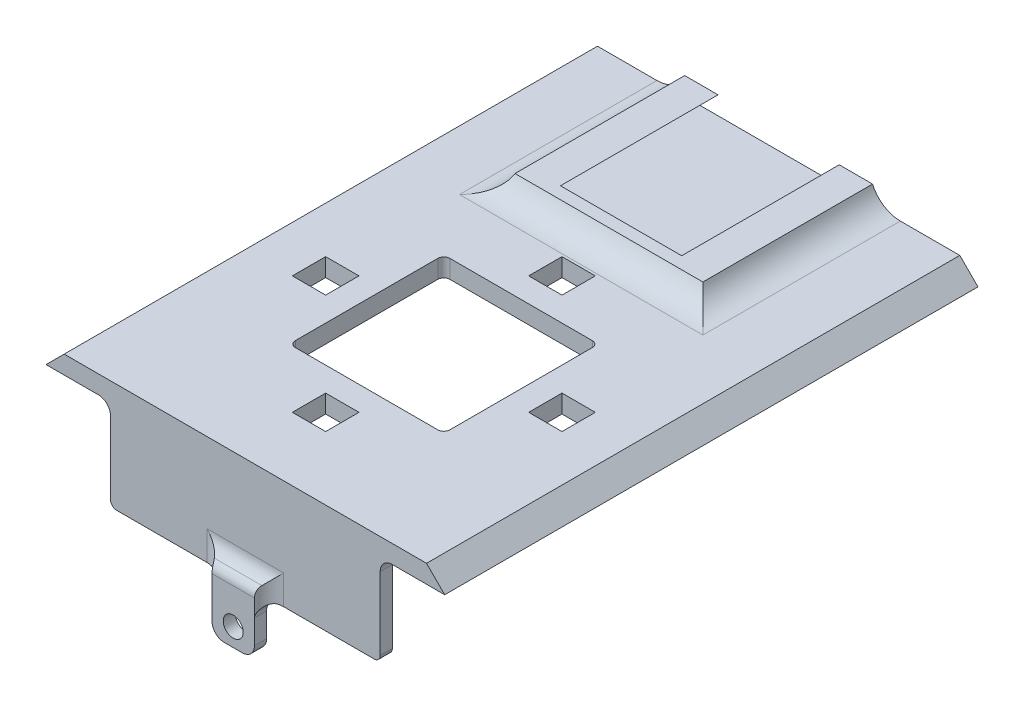
SolidWorks part; units mm, degrees
ref_plane "Front Plane" through (0, 0, 0) normal (0, 0, 1) x (1, 0, 0)
ref_plane "Top Plane" through (0, 0, 0) normal (0, 1, 0) x (1, 0, 0)
ref_plane "Right Plane" through (0, 0, 0) normal (1, 0, 0) x (0, 0, -1)
sketch "Sketch1" plane through (0, 0, 0) normal (0, 0, 1) x (1, 0, 0)
  line L0 (33.5, 0) -> (-33.5, 0) construction
  line L1 (-33.5, 0) -> (-30, 3.5) construction
  line L2 (-30, 3.5) -> (30, 3.5) construction
  line L3 (30, 3.5) -> (33.5, 0) construction
  line L4 (29.8964, 3.25) -> (32.8964, 0.25)
  line L5 (32.8964, 0.25) -> (-32.8964, 0.25)
  line L6 (-32.8964, 0.25) -> (-29.8964, 3.25)
  line L7 (-29.8964, 3.25) -> (29.8964, 3.25)
  point P4 (0, 0)
  dimension "D1" = 45
  dimension "D2" = 45
  dimension "D3" = 3
  dimension "D4" = 67
  dimension "D5" = 0.25
extrude "Boss-Extrude1" add sketch "Sketch1" against normal blind 88
sketch "Sketch2" plane through (0, 0, 0) normal (0, 0, 1) x (1, 0, 0)
  line L0 (-32.8964, 0.25) -> (32.8964, 0.25) construction
  line L1 (-22.25, 0.25) -> (22.25, 0.25)
  line L2 (-22.25, 0.25) -> (-22.25, -14.75)
  line L3 (-22.25, -14.75) -> (22.25, -14.75)
  line L4 (22.25, 0.25) -> (22.25, -14.75)
  line L5 (-22.25, 0.25) -> (22.25, -14.75) construction
  line L6 (-22.25, -14.75) -> (22.25, 0.25) construction
  point P0 (0, -7.25)
  dimension "D1" = 15
  dimension "D2" = 44.5
extrude "Boss-Extrude2" add sketch "Sketch2" against normal blind 2
sketch "Sketch3" plane through (0, 0, 0) normal (0, 0, 1) x (1, 0, 0)
  line L0 (-22.25, -14.75) -> (22.25, -14.75) construction
  line L1 (3.5, -22.75) -> (-3.5, -22.75)
  line L2 (3.5, -22.75) -> (3.5, -12.75)
  line L3 (3.5, -12.75) -> (-3.5, -12.75)
  line L4 (-3.5, -22.75) -> (-3.5, -12.75)
  line L5 (3.5, -22.75) -> (-3.5, -12.75) construction
  line L6 (3.5, -12.75) -> (-3.5, -22.75) construction
  circle A0 centre (0, -19.75) radius 1.65
  point P0 (0, -17.75)
  dimension "D4" = 3.3
  dimension "D1" = 8
  dimension "D2" = 2
  dimension "D3" = 7
  dimension "D5" = 5
extrude "Boss-Extrude3" add sketch "Sketch3" along normal blind 2
fillet "Fillet1" radius 3 3 edges at (3.5, -13.75, 0) (-3.5, -13.75, 0) (0, -12.75, 0)
fillet "Fillet2" radius 2 2 edges at (3.5, -14.75, 1) (-3.5, -14.75, 1)
fillet "Fillet3" radius 2 2 edges at (-3.5, -22.75, 1) (3.5, -22.75, 1)
fillet "Fillet4" radius 2 1 edges at (0, -12.75, 2)
fillet "Fillet5" radius 0.5 1 edges at (0, -14.75, 0)
fillet "Fillet6" radius 1 2 edges at (22.25, -14.75, -1) (-22.25, -14.75, -1)
fillet "Fillet7" radius 2 3 edges at (22.25, 0.25, -1) (0, 0.25, -2) (-22.25, 0.25, -1)
sketch "Sketch4" plane through (0, 3.25, 0) normal (0, 1, 0) x (1, 0, 0)
  line L0 (29.8964, 0) -> (-29.8964, 0) construction
  line L1 (12.75, 20) -> (-12.75, 20)
  line L2 (12.75, 20) -> (12.75, 45.5)
  line L3 (12.75, 45.5) -> (-12.75, 45.5)
  line L4 (-12.75, 20) -> (-12.75, 45.5)
  line L5 (12.75, 20) -> (-12.75, 45.5) construction
  line L6 (12.75, 45.5) -> (-12.75, 20) construction
  line L7 (-19.5, 32.75) -> (19.5, 32.75) construction
  line L8 (2.75, 16) -> (-2.75, 16)
  line L9 (2.75, 16) -> (2.75, 10.5)
  line L10 (2.75, 10.5) -> (-2.75, 10.5)
  line L11 (-2.75, 16) -> (-2.75, 10.5)
  line L12 (2.75, 16) -> (-2.75, 10.5) construction
  line L13 (2.75, 10.5) -> (-2.75, 16) construction
  line L14 (22.25, 35.5) -> (16.75, 35.5)
  line L15 (22.25, 35.5) -> (22.25, 30)
  line L16 (22.25, 30) -> (16.75, 30)
  line L17 (16.75, 35.5) -> (16.75, 30)
  line L18 (22.25, 35.5) -> (16.75, 30) construction
  line L19 (22.25, 30) -> (16.75, 35.5) construction
  line L20 (-16.75, 35.5) -> (-22.25, 35.5)
  line L21 (-16.75, 35.5) -> (-16.75, 30)
  line L22 (-16.75, 30) -> (-22.25, 30)
  line L23 (-22.25, 35.5) -> (-22.25, 30)
  line L24 (-16.75, 35.5) -> (-22.25, 30) construction
  line L25 (-16.75, 30) -> (-22.25, 35.5) construction
  line L26 (2.75, 55) -> (-2.75, 55)
  line L27 (2.75, 55) -> (2.75, 49.5)
  line L28 (2.75, 49.5) -> (-2.75, 49.5)
  line L29 (-2.75, 55) -> (-2.75, 49.5)
  line L30 (2.75, 55) -> (-2.75, 49.5) construction
  line L31 (2.75, 49.5) -> (-2.75, 55) construction
  line L32 (0, 52.25) -> (0, 13.25) construction
  point P0 (0, 32.75)
  point P5 (19.5, 32.75)
  point P8 (0, 13.25)
  point P18 (-19.5, 32.75)
  point P23 (0, 52.25)
  point P28 (0, 32.75)
  point P34 (0, 32.75)
  dimension "D1" = 25.5
  dimension "D2" = 25.5
  dimension "D3" = 20
  dimension "D4" = 5.5
  dimension "D5" = 5.5
  dimension "D6" = 33.5
  dimension "D7" = 33.5
extrude "Cut-Extrude1" cut sketch "Sketch4" against normal up to surface (3 mm away) up to face at (0, 0.25, -23)
fillet "Fillet8" radius 1 4 edges at (-12.75, 1.75, -45.5) (-12.75, 1.75, -20) (12.75, 1.75, -20) (12.75, 1.75, -45.5)
sketch "Sketch6" plane through (0, 0, -88) normal (0, 0, -1) x (-1, 0, 0)
  line L0 (-13, 3.25) -> (-10, 6.25)
  line L1 (-29.8964, 3.25) -> (29.8964, 3.25) construction
  line L2 (-10, 6.25) -> (-15.5, 6.25)
  line L3 (-15.5, 6.25) -> (-15.5, 3.25)
  line L4 (-15.5, 3.25) -> (-13, 3.25)
  line L5 (0, 0) -> (0, 6.25) construction
  line L6 (15.5, 6.25) -> (15.5, 3.25)
  line L7 (10, 6.25) -> (15.5, 6.25)
  line L8 (13, 3.25) -> (10, 6.25)
  line L9 (15.5, 3.25) -> (13, 3.25)
  dimension "D1" = 3
  dimension "D2" = 2.5
  dimension "D3" = 45
  dimension "D4" = 13
extrude "Boss-Extrude4" add sketch "Sketch6" against normal blind 28
sketch "Sketch7" plane through (-15.5, 0, 0) normal (-1, 0, 0) x (0, 0, 1)
  line L0 (-62, 6.25) -> (-60, 6.25)
  line L1 (-60, 6.25) -> (-88, 6.25) construction
  line L2 (-60, 6.25) -> (-60, 3.25)
  line L3 (-60, 3.25) -> (-62, 3.25)
  line L4 (-60, 3.25) -> (-88, 3.25) construction
  line L5 (-62, 3.25) -> (-62, 6.25)
  dimension "D1" = 2
extrude "Boss-Extrude5" add sketch "Sketch7" against normal up to surface (28.5 mm away) up to face at (11.5, 4.75, -74)
fillet "Fillet9" radius 5 3 edges at (0, 3.25, -60) (-15.5, 3.25, -74) (15.5, 3.25, -74)
